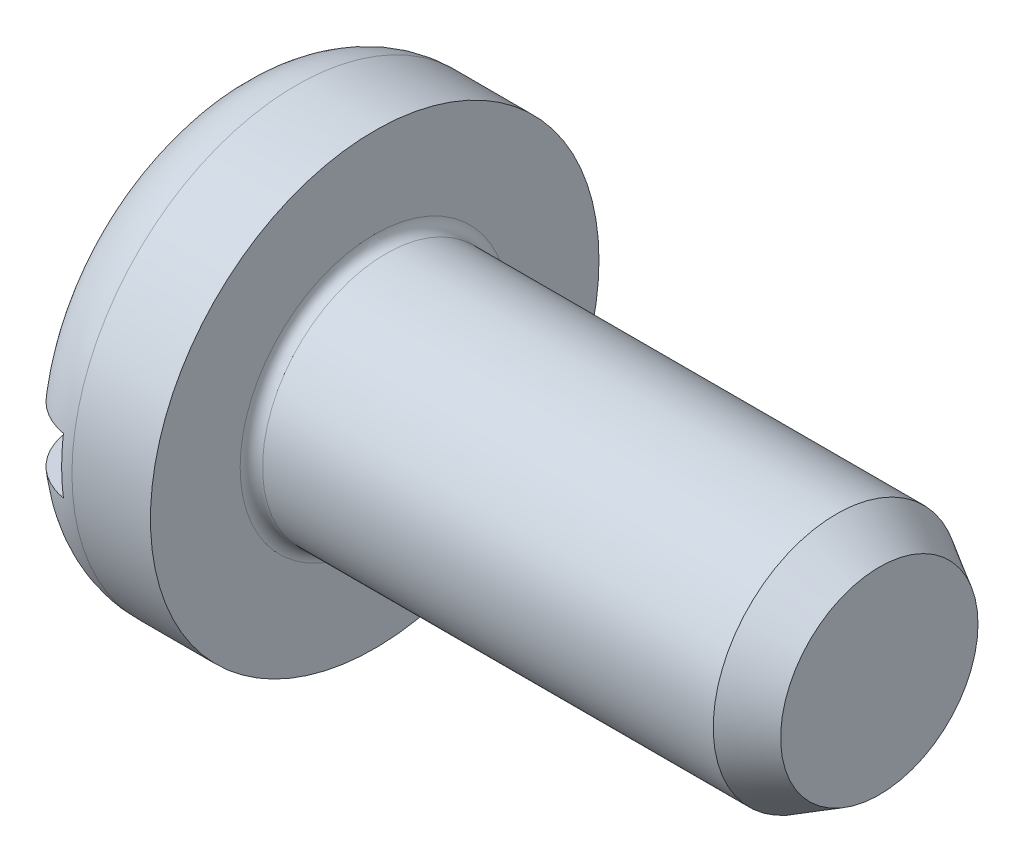
SolidWorks part; units mm, degrees
ref_plane "Front" through (0, 0, 0) normal (0, 0, 1) x (1, 0, 0)
ref_plane "Top" through (0, 0, 0) normal (0, 1, 0) x (1, 0, 0)
ref_plane "Right" through (0, 0, 0) normal (1, 0, 0) x (0, 0, -1)
sketch "Sketch1" plane through (0, 0, 0) normal (0, 0, 1) x (1, 0, 0)
  line L0 (0, 0) -> (0, 2)
  line L1 (0, 2) -> (1.3, 2)
  line L2 (1.3, 2) -> (1.3, 1.1)
  line L4 (1.3, 1.1) -> (5.8, 1.1)
  line L5 (5.8, 1.1) -> (5.8, 0)
  line L6 (5.8, 0) -> (0, 0)
  line L7 (13.1079, 0) -> (-2.2203, 0) construction
revolve "Revolve1" add sketch "Sketch1" angle 360 about L7
cosmetic thread "ThreadCosmetic" [suppressed] parameters "D2"=1.63
chamfer "Chamfer1" distance 0.22 angle 60 1 edges at (5.8, 0, -1.1) first distance on face at (5.8, 0, -1.1)
sketch "Sketch6" plane through (0, 0, 0) normal (0, 0, 1) x (1, 0, 0)
  line L0 (2.0155, 0.815) -> (1.5445, 0.815)
  line L1 (1.5445, 0.815) -> (1.38, 1.1)
  line L2 (2.0155, 0.815) -> (2.18, 1.1)
  line L3 (1.38, 1.1) -> (1.38, 1.35)
  line L4 (2.18, 1.1) -> (2.18, 1.35)
  line L5 (1.38, 1.35) -> (2.18, 1.35)
  line L6 (1.78, 0.815) -> (1.78, 0) construction
  line L7 (0, 0) -> (7.3035, 0) construction
  dimension "D2" = 60
  dimension "D3" = 0.25
  dimension "minordia" = 1.63
  dimension "threadstart" = 1.78
  dimension "D1" = 2.2
revolve "ThreadSchematic" [suppressed] cut sketch "Sketch6" angle 360 about L7
pattern_linear "ThdSchPat" [suppressed] count 6 spacing 0.8 along (1, 0, 0) of bodies 139
sketch "Sketch5" plane through (0, 0, 0) normal (0, 0, 1) x (1, 0, 0)
  line L1 (5.8, 1.1) -> (5.8, 0) construction
  line L3 (3.5, -1.1) -> (4, -1.1) construction
  line L4 (0, 0) -> (6.648, 0) construction
  line L5 (5.8, 0) -> (4, -1.1)
  line L6 (5.8, 0) -> (6, 0)
  line L7 (6, 0) -> (6, -1.3)
  line L8 (6, -1.3) -> (4, -1.3)
  line L9 (4, -1.3) -> (4, -1.1)
  line L10 (4, -1.1) -> (6.8602, -1.1) construction
  dimension "D4" = 2.2
  dimension "y" = 2
revolve "EndCone" [suppressed] cut sketch "Sketch5" angle 360 about L4
fillet "Fillet1" radius 0.1 1 edges at (1.3, 0, -1.1)
fillet "Fillet2" radius 0.6 1 edges at (0, 0, -2)
sketch "Sketch7" plane through (0, 0, 0) normal (0, 0, 1) x (1, 0, 0)
  line L0 (0, 0) -> (-1.1882, 0) construction
  line L1 (-1, 0.25) -> (0.5, 0.25)
  line L2 (-1, 0.25) -> (-1, -0.25)
  line L3 (-1, -0.25) -> (0.5, -0.25)
  line L4 (0.5, 0.25) -> (0.5, -0.25)
  dimension "D1" = 1
  dimension "n" = 0.5
  dimension "t" = 0.5
extrude "Slot" cut sketch "Sketch7" against normal mid plane 30
equation "\"minordia@Sketch6\" = \"D2@ThreadCosmetic\""
equation "\"D1@Chamfer1\" = \"d@Sketch1\" / 10"
equation "\"D1@ThdSchPat\" = int((\"l@Sketch1\"/\"advance@Sketch6\") + 0.8)"
equation "\"D3@ThdSchPat\" = \"advance@Sketch6\""
equation "\"D1@Sketch6\" = \"d@Sketch1\""
equation "\"D4@Sketch5\" = \"d@Sketch1\""
equation "\"threadstart@Sketch6\" = \"k@Sketch1\" + \"advance@Sketch6\" * 0.6"
